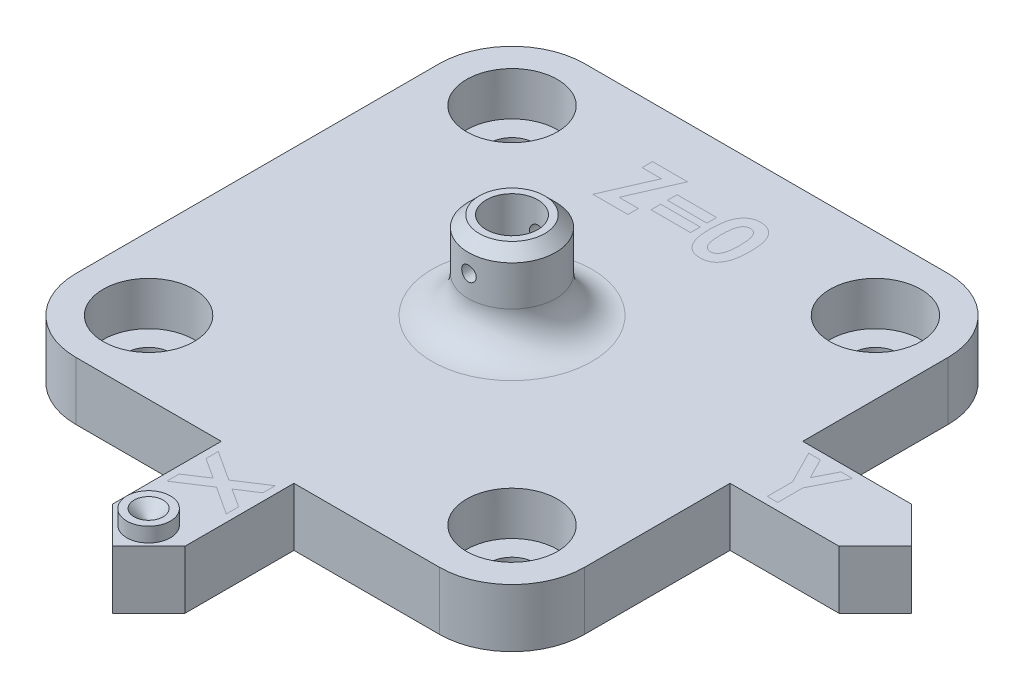
SolidWorks part; units mm, degrees
ref_plane "Front Plane" through (0, 0, 0) normal (0, 0, 1) x (1, 0, 0)
ref_plane "Top Plane" through (0, 0, 0) normal (0, 1, 0) x (1, 0, 0)
ref_plane "Right Plane" through (0, 0, 0) normal (1, 0, 0) x (0, 0, -1)
sketch "Sketch1" plane through (0, 0, 0) normal (0, 1, 0) x (1, 0, 0)
  line L1 (-31, 6) -> (31, 6) construction
  line L2 (-31, 6) -> (-31, -6) construction
  line L3 (-31, -6) -> (31, -6) construction
  line L4 (31, 6) -> (31, -6) construction
  line L5 (-31, 6) -> (31, -6) construction
  line L6 (-31, -6) -> (31, 6) construction
  line L7 (-35, -35) -> (35, -35)
  line L8 (-35, -35) -> (-35, 35)
  line L9 (-35, 35) -> (35, 35)
  line L10 (35, -35) -> (35, 35)
  line L11 (-35, -35) -> (35, 35) construction
  line L12 (-35, 35) -> (35, -35) construction
  circle A0 centre (-25, 0) radius 3.1 construction
  circle A1 centre (25, 0) radius 3.1 construction
  circle A2 centre (0, 0) radius 45 construction
  circle A3 centre (-25, 25) radius 3.1 construction
  circle A4 centre (-25, -75) radius 3.1 construction
  point P0 (0, 0)
  point P14 (0, 0)
  dimension "D2" = 6.2
  dimension "D7" = 90
  dimension "D1" = 12
  dimension "D3" = 6
  dimension "D4" = 25
  dimension "D5" = 25
  dimension "D6" = 25
  dimension "D8" = 100
  dimension "D9" = 10
  dimension "D10" = 10
extrude "Boss-Extrude1" add sketch "Sketch1" along normal blind 8
sketch "Sketch2" plane through (0, 8, 0) normal (0, 1, 0) x (1, 0, 0)
  circle A0 centre (25, 0) radius 3.1 construction
  circle A1 centre (-25, 0) radius 3.1 construction
  circle A2 centre (25, 0) radius 3.1 construction
  circle A3 centre (-25, 0) radius 3.1 construction
  circle A4 centre (-25, 25) radius 3.1 construction
  circle A5 centre (-25, 25) radius 3.1
extrude "Cut-Extrude1" cut sketch "Sketch2" against normal through all
sketch "Sketch8" plane through (0, 8, 0) normal (0, 1, 0) x (1, 0, 0)
  circle A0 centre (-25, 25) radius 6.25
  dimension "D1" = 12.5
extrude "Cut-Extrude6" cut sketch "Sketch8" against normal offset from surface (6 mm away) 2 up to face at (-25, 0, -21.9)
pattern_linear "LPattern1" count 2 spacing 50 along (1, 0, 0) count 2 spacing 50 along (0, 0, 1) of "Cut-Extrude6", "Cut-Extrude1"
sketch "Sketch3" plane through (0, 8, 0) normal (0, 1, 0) x (1, 0, 0)
  line L1 (-6, 6) -> (6, 6) construction
  line L2 (-6, 6) -> (-6, -6) construction
  line L3 (-6, -6) -> (6, -6) construction
  line L4 (6, 6) -> (6, -6) construction
  line L5 (-6, 6) -> (6, -6) construction
  line L6 (-6, -6) -> (6, 6) construction
  line L7 (-31, 6) -> (31, -6) construction
  circle A0 centre (0, 0) radius 6
  point P0 (0, 0)
  dimension "D1" = 12
extrude "Boss-Extrude2" add sketch "Sketch3" along normal blind 12
sketch "Sketch4" plane through (0, 20, 0) normal (0, 1, 0) x (1, 0, 0)
  circle A0 centre (0, 0) radius 3.55
  dimension "D1" = 7.1
extrude "Cut-Extrude2" cut sketch "Sketch4" against normal offset from surface (11 mm away) 1 up to face at (0, 8, -6)
sketch "Sketch5" plane through (0, 9, 0) normal (0, 1, 0) x (1, 0, 0)
  circle A0 centre (0, 0) radius 3.05
  circle A1 centre (0, 0) radius 3.55 construction
  dimension "D1" = 0.5
extrude "Cut-Extrude3" cut sketch "Sketch5" against normal through all
fillet "Fillet1" radius 5 1 edges at (0, 8, -6)
sketch "Sketch7" plane through (0, 0, 0) normal (0, 0, -1) x (-1, 0, 0)
  line L1 (6, 20) -> (-6, 20) construction
  circle A0 centre (0, 16) radius 1
  dimension "D1" = 2
  dimension "D2" = 4
extrude "Cut-Extrude5" cut sketch "Sketch7" against normal through all both and the other way through all
chamfer "Chamfer2" distance 1.5 angle 45 1 edges at (0, 20, 6)
sketch "Sketch9" plane through (0, 0, 0) normal (0, 1, 0) x (1, 0, 0)
  line L0 (-35, -35) -> (35, -35) construction
  line L1 (-5, -55) -> (5, -55)
  line L2 (-5, -55) -> (-5, -35)
  line L3 (-5, -35) -> (5, -35)
  line L4 (5, -55) -> (5, -35)
  line L5 (-5, -55) -> (5, -35) construction
  line L6 (-5, -35) -> (5, -55) construction
  line L7 (35, -35) -> (35, 35) construction
  line L8 (55, -5) -> (35, -5)
  line L9 (55, -5) -> (55, 5)
  line L10 (55, 5) -> (35, 5)
  line L11 (35, -5) -> (35, 5)
  line L12 (55, -5) -> (35, 5) construction
  line L13 (55, 5) -> (35, -5) construction
  point P0 (0, -45)
  point P7 (45, 0)
  dimension "D1" = 10
  dimension "D2" = 20
extrude "Boss-Extrude3" add sketch "Sketch9" along normal up to surface (8 mm away) up to face at (0, 8, -11)
chamfer "Chamfer3" distance 5 angle 45 4 edges at (55, 4, -5) (55, 4, 5) (5, 4, 55) (-5, 4, 55)
sketch "Sketch10" plane through (0, 8, 0) normal (0, 1, 0) x (1, 0, 0)
  line L0 (30, -4) -> (50, -4) construction
  line L1 (-4, -50) -> (-4, -30) construction
  line L2 (50, -5) -> (35, -5) construction
  line L3 (-5, -50) -> (-5, -35) construction
  line L4 (-35, -35) -> (-5, -35) construction
  line L5 (35, -35) -> (35, -5) construction
  line L6 (-15, 20) -> (15, 20) construction
  text T0 "X" font "Century Gothic" height 8
  text T1 "Y" font "Century Gothic" height 8
  text T2 "Z=0" font "Century Gothic" height 8
  point P7 (0, 20)
  dimension "D1" = 20
  dimension "D4" = 5
  dimension "D5" = 5
  dimension "D6" = 20
  dimension "D7" = 30
extrude "Cut-Extrude7" cut sketch "Sketch10" against normal blind 1
sketch "Sketch16" plane through (0, 7, 0) normal (0, 1, 0) x (1, 0, 0)
  line L0 (0.133, -40.7917) -> (4, -43.3093) construction
  line L1 (4, -43.3093) -> (4, -41.617) construction
  line L2 (4, -41.617) -> (1.4311, -39.9455) construction
  line L3 (1.4311, -39.9455) -> (4, -38.2708) construction
  line L4 (4, -38.2708) -> (4, -36.5737) construction
  line L5 (4, -36.5737) -> (0.1298, -39.0978) construction
  line L6 (0.1298, -39.0978) -> (-4, -36.4103) construction
  line L7 (-4, -36.4103) -> (-4, -38.1026) construction
  line L8 (-8.6667, 28) -> (-8.6667, 26.5641)
  line L9 (-8.6667, 26.5641) -> (-6.0096, 26.5641)
  line L10 (-6.0096, 26.5641) -> (-8.8718, 20)
  line L11 (-8.8718, 20) -> (-4.0513, 20)
  line L12 (-4.0513, 20) -> (-4.0513, 21.4359)
  line L13 (-4.0513, 21.4359) -> (-6.7099, 21.4359)
  line L14 (-6.7099, 21.4359) -> (-3.8462, 28)
  line L15 (-3.8462, 28) -> (-8.6667, 28)
  line L16 (-8.6667, 28) -> (-8.6667, 26.5641)
  line L17 (-8.6667, 26.5641) -> (-6.0096, 26.5641)
  line L18 (-6.0096, 26.5641) -> (-8.8718, 20)
  line L19 (-8.8718, 20) -> (-4.0513, 20)
  line L20 (-4.0513, 20) -> (-4.0513, 21.4359)
  line L21 (-4.0513, 21.4359) -> (-6.7099, 21.4359)
  line L22 (-6.7099, 21.4359) -> (-3.8462, 28)
  line L23 (-3.8462, 28) -> (-8.6667, 28)
  line L24 (-4, -38.1026) -> (-1.1683, -39.9455) construction
  line L25 (-1.1683, -39.9455) -> (-4, -41.7917) construction
  line L26 (-4, -41.7917) -> (-4, -43.4872) construction
  line L27 (-4, -43.4872) -> (0.133, -40.7917) construction
  line L28 (36.8205, 4) -> (39.1282, -0.5353) construction
  line L29 (39.1282, -0.5353) -> (39.1282, -4) construction
  line L30 (39.1282, -4) -> (40.5641, -4) construction
  line L31 (40.5641, -4) -> (40.5641, -0.5353) construction
  line L32 (40.5641, -0.5353) -> (42.8718, 4) construction
  line L33 (42.8718, 4) -> (41.2772, 4) construction
  line L34 (41.2772, 4) -> (39.8462, 1.1923) construction
  line L35 (39.8462, 1.1923) -> (38.4183, 4) construction
  line L36 (38.4183, 4) -> (36.8205, 4) construction
  line L37 (-3.0256, 23.4872) -> (-3.0256, 22.1538) construction
  line L38 (-3.0256, 22.1538) -> (2.4103, 22.1538) construction
  line L39 (2.4103, 22.1538) -> (2.4103, 23.4872) construction
  line L40 (2.4103, 23.4872) -> (-3.0256, 23.4872) construction
  line L41 (-3.0256, 25.7436) -> (-3.0256, 24.4103) construction
  line L42 (-3.0256, 24.4103) -> (2.4103, 24.4103) construction
  line L43 (2.4103, 24.4103) -> (2.4103, 25.7436) construction
  line L44 (2.4103, 25.7436) -> (-3.0256, 25.7436) construction
  line L45 (0.133, -40.7917) -> (4, -43.3093)
  line L46 (4, -43.3093) -> (4, -41.617)
  line L47 (4, -41.617) -> (1.4311, -39.9455)
  line L48 (1.4311, -39.9455) -> (4, -38.2708)
  line L49 (4, -38.2708) -> (4, -36.5737)
  line L50 (4, -36.5737) -> (0.1298, -39.0978)
  line L51 (0.1298, -39.0978) -> (-4, -36.4103)
  line L52 (-4, -36.4103) -> (-4, -38.1026)
  line L53 (-4, -38.1026) -> (-1.1683, -39.9455)
  line L54 (-1.1683, -39.9455) -> (-4, -41.7917)
  line L55 (-4, -41.7917) -> (-4, -43.4872)
  line L56 (-4, -43.4872) -> (0.133, -40.7917)
  line L57 (36.8205, 4) -> (39.1282, -0.5353)
  line L58 (39.1282, -0.5353) -> (39.1282, -4)
  line L59 (39.1282, -4) -> (40.5641, -4)
  line L60 (40.5641, -4) -> (40.5641, -0.5353)
  line L61 (40.5641, -0.5353) -> (42.8718, 4)
  line L62 (42.8718, 4) -> (41.2772, 4)
  line L63 (41.2772, 4) -> (39.8462, 1.1923)
  line L64 (39.8462, 1.1923) -> (38.4183, 4)
  line L65 (38.4183, 4) -> (36.8205, 4)
  line L66 (-3.0256, 23.4872) -> (-3.0256, 22.1538)
  line L67 (-3.0256, 22.1538) -> (2.4103, 22.1538)
  line L68 (2.4103, 22.1538) -> (2.4103, 23.4872)
  line L69 (2.4103, 23.4872) -> (-3.0256, 23.4872)
  line L70 (-3.0256, 25.7436) -> (-3.0256, 24.4103)
  line L71 (-3.0256, 24.4103) -> (2.4103, 24.4103)
  line L72 (2.4103, 24.4103) -> (2.4103, 25.7436)
  line L73 (2.4103, 25.7436) -> (-3.0256, 25.7436)
  spline S0 degree 3 poles (-131.7963, 2023.3736) (22.2514, -1.7136) (12.5985, 29.3312) (5.4123, 28.1449) (5.1283, 28.0594) (4.8631, 27.9383) (4.6145, 27.7848) (4.3863, 27.5948) (-0.5437, 22.4383) (20.4757, -3.4865) (-1566.3999, 1265.3933) knots -8.647948 -8.647948 -8.647948 -8.647948 0.131719 0.257624 0.379077 0.499465 0.619088 0.7413 0.867686 9.462064 9.462064 9.462064 9.462064 only from (6.0272, 28.2051) to (3.9904, 27.117) construction
  spline S1 degree 3 poles (-1757.1302, 974.8805) (38.1042, 24.2048) (6.4362, 33.0366) (3.6959, 26.5373) (3.5815, 26.1941) (3.4922, 25.8118) (3.42, 25.3929) (3.3708, 24.9358) (2.4817, 11.8092) (31.1626, -2.1567) (-1996.277, 53.0675) knots -6.083186 -6.083186 -6.083186 -6.083186 0.093438 0.194013 0.303383 0.421624 0.550096 0.689211 0.838929 12.491567 12.491567 12.491567 12.491567 only from (3.9904, 27.117) to (3.3333, 23.9215) construction
  spline S2 degree 3 poles (-1996.5438, 19.6483) (24.8472, 47.8074) (2.8103, 35.3289) (3.3516, 23.185) (3.3788, 22.8467) (3.4153, 22.5307) (3.4611, 22.2369) (3.5179, 21.9659) (3.5874, 21.7179) (3.6654, 21.4906) (3.7552, 21.2822) (3.8507, 21.0881) (3.9548, 20.908) (4.0676, 20.7422) (4.1879, 20.5888) (4.3175, 20.4499) (4.4546, 20.3239) (4.5988, 20.2112) (4.7524, 20.1128) (4.9149, 20.0275) (5.0867, 19.9559) (5.2664, 19.8958) (5.455, 19.8521) (5.6512, 19.8174) (12.3124, 19.2077) (19.7932, 41.6831) (-51.1933, -1979.22) knots -6.292704 -6.292704 -6.292704 -6.292704 0.068139 0.132344 0.192691 0.249232 0.302052 0.351311 0.396892 0.439446 0.479424 0.517927 0.554843 0.590345 0.62485 0.658737 0.691624 0.724128 0.756313 0.788829 0.82192 0.855546 0.889842 0.925133 0.961783 4.454699 4.454699 4.454699 4.454699 only from (3.3333, 23.9215) to (6.0689, 19.7949) construction
  spline S3 degree 3 poles (65.7357, -1979.2509) (-7.5781, 41.8788) (-0.1196, 19.2043) (6.4856, 19.8175) (6.6807, 19.852) (6.8678, 19.8954) (7.044, 19.956) (7.2122, 20.0256) (7.3694, 20.1114) (7.5184, 20.2095) (7.6576, 20.3231) (7.7922, 20.4479) (7.9165, 20.5904) (8.0358, 20.7451) (8.1445, 20.9174) (8.2483, 21.1022) (8.3451, 21.3022) (8.433, 21.518) (8.5147, 21.7521) (8.5824, 22.0084) (8.6393, 22.2862) (8.6879, 22.5855) (8.7234, 22.9071) (8.751, 23.2507) (9.2905, 35.5845) (-12.6765, 48.2224) (2008.6272, 22.718) knots -3.400415 -3.400415 -3.400415 -3.400415 0.037939 0.07404 0.109073 0.142844 0.175687 0.207645 0.239175 0.270414 0.302015 0.334248 0.367526 0.402053 0.437693 0.475324 0.514308 0.555299 0.598705 0.645592 0.695599 0.748917 0.806171 0.866923 0.931509 7.344595 7.344595 7.344595 7.344595 only from (6.0689, 19.7949) to (8.7692, 23.9968) construction
  spline S4 degree 3 poles (2008.5884, 35.2807) (-13.1687, 0.4734) (9.3051, 12.8122) (8.7503, 24.7353) (8.7257, 25.0765) (8.6893, 25.3957) (8.641, 25.693) (8.5839, 25.9685) (8.5173, 26.2231) (8.4382, 26.4567) (8.3497, 26.6721) (8.2533, 26.8725) (8.1477, 27.0582) (8.0338, 27.2302) (7.912, 27.3885) (7.7795, 27.5316) (7.6393, 27.6618) (7.4888, 27.7759) (7.3316, 27.8767) (7.1677, 27.966) (6.9951, 28.0393) (6.8158, 28.1006) (6.6286, 28.1469) (6.4347, 28.1801) (0.3921, 28.8398) (-6.9063, 4.7286) (94.9906, 2026.067) knots -6.101207 -6.101207 -6.101207 -6.101207 0.067325 0.131046 0.191211 0.247637 0.300428 0.349925 0.395975 0.439087 0.479887 0.518688 0.556281 0.592452 0.627384 0.661471 0.69516 0.728117 0.760933 0.793574 0.826381 0.859694 0.893374 0.927966 0.963365 4.094396 4.094396 4.094396 4.094396 only from (8.7692, 23.9968) to (6.0272, 28.2051) construction
  spline S5 degree 3 poles (6.0272, 28.2051) (5.9213, 28.2016) (5.7141, 28.1947) (5.4123, 28.1449) (5.1283, 28.0594) (4.8631, 27.9383) (4.6145, 27.7848) (4.3863, 27.5948) (4.174, 27.3727) (4.0525, 27.2035) (3.9904, 27.117) knots 0 0 0 0 0.131719 0.257624 0.379077 0.499465 0.619088 0.7413 0.867686 1 1 1 1
  spline S6 degree 3 poles (3.9904, 27.117) (3.937, 27.0289) (3.826, 26.846) (3.6959, 26.5373) (3.5815, 26.1941) (3.4922, 25.8118) (3.42, 25.3929) (3.3708, 24.9358) (3.3373, 24.4412) (3.3347, 24.0989) (3.3333, 23.9215) knots 0 0 0 0 0.093438 0.194013 0.303383 0.421624 0.550096 0.689211 0.838929 1 1 1 1
  spline S7 degree 3 poles (3.3333, 23.9215) (3.3341, 23.7938) (3.3356, 23.5458) (3.3516, 23.185) (3.3788, 22.8467) (3.4153, 22.5307) (3.4611, 22.2369) (3.5179, 21.9659) (3.5874, 21.7179) (3.6654, 21.4906) (3.7552, 21.2822) (3.8507, 21.0881) (3.9548, 20.908) (4.0676, 20.7422) (4.1879, 20.5888) (4.3175, 20.4499) (4.4546, 20.3239) (4.5988, 20.2112) (4.7524, 20.1128) (4.9149, 20.0275) (5.0867, 19.9559) (5.2664, 19.8958) (5.455, 19.8521) (5.6512, 19.8174) (5.857, 19.7985) (5.9973, 19.7961) (6.0689, 19.7949) knots 0 0 0 0 0.068139 0.132344 0.192691 0.249232 0.302052 0.351311 0.396892 0.439446 0.479424 0.517927 0.554843 0.590345 0.62485 0.658737 0.691624 0.724128 0.756313 0.788829 0.82192 0.855546 0.889842 0.925133 0.961783 1 1 1 1
  spline S8 degree 3 poles (6.0689, 19.7949) (6.1405, 19.7961) (6.2803, 19.7984) (6.4856, 19.8175) (6.6807, 19.852) (6.8678, 19.8954) (7.044, 19.956) (7.2122, 20.0256) (7.3694, 20.1114) (7.5184, 20.2095) (7.6576, 20.3231) (7.7922, 20.4479) (7.9165, 20.5904) (8.0358, 20.7451) (8.1445, 20.9174) (8.2483, 21.1022) (8.3451, 21.3022) (8.433, 21.518) (8.5147, 21.7521) (8.5824, 22.0084) (8.6393, 22.2862) (8.6879, 22.5855) (8.7234, 22.9071) (8.751, 23.2507) (8.767, 23.6163) (8.7685, 23.8675) (8.7692, 23.9968) knots 0 0 0 0 0.037939 0.07404 0.109073 0.142844 0.175687 0.207645 0.239175 0.270414 0.302015 0.334248 0.367526 0.402053 0.437693 0.475324 0.514308 0.555299 0.598705 0.645592 0.695599 0.748917 0.806171 0.866923 0.931509 1 1 1 1
  spline S9 degree 3 poles (8.7692, 23.9968) (8.7685, 24.1245) (8.7671, 24.373) (8.7503, 24.7353) (8.7257, 25.0765) (8.6893, 25.3957) (8.641, 25.693) (8.5839, 25.9685) (8.5173, 26.2231) (8.4382, 26.4567) (8.3497, 26.6721) (8.2533, 26.8725) (8.1477, 27.0582) (8.0338, 27.2302) (7.912, 27.3885) (7.7795, 27.5316) (7.6393, 27.6618) (7.4888, 27.7759) (7.3316, 27.8767) (7.1677, 27.966) (6.9951, 28.0393) (6.8158, 28.1006) (6.6286, 28.1469) (6.4347, 28.1801) (6.2334, 28.2021) (6.0967, 28.2041) (6.0272, 28.2051) knots 0 0 0 0 0.067325 0.131046 0.191211 0.247637 0.300428 0.349925 0.395975 0.439087 0.479887 0.518688 0.556281 0.592452 0.627384 0.661471 0.69516 0.728117 0.760933 0.793574 0.826381 0.859694 0.893374 0.927966 0.963365 1 1 1 1
  spline S15 degree 3 poles (3006.8723, 64.4156) (-23.2912, -1.2869) (7.9892, 12.0725) (7.3132, 24.714) (7.2872, 25.0323) (7.2493, 25.3196) (7.2004, 25.5768) (7.1402, 25.8037) (7.0693, 26.0008) (6.9851, 26.1679) (6.8919, 26.31) (6.793, 26.4318) (6.6879, 26.5359) (6.5768, 26.6225) (6.4572, 26.6887) (6.3313, 26.7354) (2.0838, 27.6423) (-5.7225, -5.7114) (307.3534, 3011.3674) knots -10.943971 -10.943971 -10.943971 -10.943971 0.112115 0.215802 0.310203 0.395993 0.47341 0.542778 0.604548 0.659357 0.708764 0.755356 0.798687 0.840017 0.880203 0.919733 0.959049 4.723306 4.723306 4.723306 4.723306 only from (7.3333, 23.9968) to (6.0625, 26.7692)
  spline S16 degree 3 poles (-396.7877, 2999.2649) (20.9753, -12.5004) (10.4324, 28.0237) (5.6977, 26.7109) (5.5292, 26.6343) (5.401, 26.5422) (5.305, 26.4539) (5.238, 26.374) (5.1733, 26.2848) (5.1162, 26.1823) (5.0623, 26.0702) (5.0096, 25.9481) (4.9664, 25.8128) (4.9239, 25.6666) (4.8867, 25.5057) (4.8556, 25.3285) (4.8278, 25.1341) (4.8083, 24.9222) (4.7902, 24.693) (4.7773, 24.4462) (4.4295, 7.4879) (21.3435, -9.4959) (-2994.7669, -7.4366) knots -4.028583 -4.028583 -4.028583 -4.028583 0.053834 0.105543 0.158054 0.211987 0.240207 0.269794 0.301343 0.334608 0.370284 0.408089 0.448681 0.492069 0.538664 0.590371 0.646388 0.707195 0.772947 0.843643 0.919308 15.328481 15.328481 15.328481 15.328481 only from (6.0625, 26.7692) to (4.7692, 23.9054)
  spline S17 degree 3 poles (-2994.933, 19.8201) (30.7114, 51.9921) (4.1649, 37.4469) (4.7882, 23.2142) (4.8177, 22.9085) (4.8544, 22.631) (4.9059, 22.3833) (4.9651, 22.1633) (5.0383, 21.9737) (5.1229, 21.8117) (5.2166, 21.6739) (5.3182, 21.5568) (5.4245, 21.4553) (5.5386, 21.3729) (5.6603, 21.3098) (5.7886, 21.2644) (10.1593, 20.3639) (17.9321, 53.1736) (-286.2462, -2964.186) knots -12.639915 -12.639915 -12.639915 -12.639915 0.110734 0.212341 0.305502 0.389835 0.46669 0.535262 0.596763 0.651066 0.701036 0.74786 0.791833 0.834284 0.875334 0.916035 0.957652 4.913375 4.913375 4.913375 4.913375 only from (4.7692, 23.9054) to (6.0625, 21.2308)
  spline S18 degree 3 poles (288.3674, -2965.3126) (-5.2957, 53.9676) (2.1906, 20.4012) (6.3241, 21.2614) (6.4456, 21.3049) (6.5598, 21.3664) (6.667, 21.4446) (6.7667, 21.5399) (10.0814, 25.6403) (-12.3943, 47.4246) (2487.2197, -1665.6184) knots -11.232017 -11.232017 -11.232017 -11.232017 0.124035 0.242846 0.360342 0.479042 0.599334 0.725488 0.858549 15.106951 15.106951 15.106951 15.106951 only from (6.0625, 21.2308) to (6.9391, 21.7804)
  spline S19 degree 3 poles (2708.4682, -1282.2352) (-29.8064, 26.3531) (4.9751, 16.4582) (7.1178, 22.1731) (7.1839, 22.4093) (7.2408, 22.6729) (7.2797, 22.9652) (7.3132, 23.2841) (7.9635, 37.2578) (-19.872, 51.529) (3007.087, 22.3277) knots -7.73203 -7.73203 -7.73203 -7.73203 0.088871 0.186355 0.294078 0.412237 0.541778 0.682703 0.835096 18.984053 18.984053 18.984053 18.984053 only from (6.9391, 21.7804) to (7.3333, 23.9968)
  spline S20 degree 3 poles (7.3333, 23.9968) (7.3328, 24.1229) (7.3318, 24.3656) (7.3132, 24.714) (7.2872, 25.0323) (7.2493, 25.3196) (7.2004, 25.5768) (7.1402, 25.8037) (7.0693, 26.0008) (6.9851, 26.1679) (6.8919, 26.31) (6.793, 26.4318) (6.6879, 26.5359) (6.5768, 26.6225) (6.4572, 26.6887) (6.3313, 26.7354) (6.1989, 26.7637) (6.1086, 26.7673) (6.0625, 26.7692) knots 0 0 0 0 0.112115 0.215802 0.310203 0.395993 0.47341 0.542778 0.604548 0.659357 0.708764 0.755356 0.798687 0.840017 0.880203 0.919733 0.959049 1 1 1 1
  spline S21 degree 3 poles (6.0625, 26.7692) (5.9997, 26.7663) (5.8765, 26.7604) (5.6977, 26.7109) (5.5292, 26.6343) (5.401, 26.5422) (5.305, 26.4539) (5.238, 26.374) (5.1733, 26.2848) (5.1162, 26.1823) (5.0623, 26.0702) (5.0096, 25.9481) (4.9664, 25.8128) (4.9239, 25.6666) (4.8867, 25.5057) (4.8556, 25.3285) (4.8278, 25.1341) (4.8083, 24.9222) (4.7902, 24.693) (4.7773, 24.4462) (4.7718, 24.1816) (4.7701, 23.9995) (4.7692, 23.9054) knots 0 0 0 0 0.053834 0.105543 0.158054 0.211987 0.240207 0.269794 0.301343 0.334608 0.370284 0.408089 0.448681 0.492069 0.538664 0.590371 0.646388 0.707195 0.772947 0.843643 0.919308 1 1 1 1
  spline S22 degree 3 poles (4.7692, 23.9054) (4.7707, 23.7836) (4.7735, 23.5501) (4.7882, 23.2142) (4.8177, 22.9085) (4.8544, 22.631) (4.9059, 22.3833) (4.9651, 22.1633) (5.0383, 21.9737) (5.1229, 21.8117) (5.2166, 21.6739) (5.3182, 21.5568) (5.4245, 21.4553) (5.5386, 21.3729) (5.6603, 21.3098) (5.7886, 21.2644) (5.9235, 21.2366) (6.0159, 21.2327) (6.0625, 21.2308) knots 0 0 0 0 0.110734 0.212341 0.305502 0.389835 0.46669 0.535262 0.596763 0.651066 0.701036 0.74786 0.791833 0.834284 0.875334 0.916035 0.957652 1 1 1 1
  spline S23 degree 3 poles (6.0625, 21.2308) (6.1075, 21.2321) (6.1956, 21.2347) (6.3241, 21.2614) (6.4456, 21.3049) (6.5598, 21.3664) (6.667, 21.4446) (6.7667, 21.5399) (6.8583, 21.6531) (6.9116, 21.7371) (6.9391, 21.7804) knots 0 0 0 0 0.124035 0.242846 0.360342 0.479042 0.599334 0.725488 0.858549 1 1 1 1
  spline S24 degree 3 poles (6.9391, 21.7804) (6.9715, 21.8396) (7.0393, 21.9637) (7.1178, 22.1731) (7.1839, 22.4093) (7.2408, 22.6729) (7.2797, 22.9652) (7.3132, 23.2841) (7.3293, 23.6312) (7.332, 23.8718) (7.3333, 23.9968) knots 0 0 0 0 0.088871 0.186355 0.294078 0.412237 0.541778 0.682703 0.835096 1 1 1 1
  dimension "D1" = 0
  dimension "D2" = 0
extrude "Boss-Extrude5" add sketch "Sketch16" along normal up to surface (1 mm away) separate body up to face at (0.0438, 8, 39.9452)
sketch "Sketch12" plane through (0, 8, 0) normal (0, 1, 0) x (1, 0, 0)
  circle A0 centre (0, -50) radius 3
  dimension "D1" = 6
  dimension "D2" = 50
extrude "Boss-Extrude4" add sketch "Sketch12" along normal blind 2
sketch "Sketch13" plane through (0, 10, 0) normal (0, 1, 0) x (1, 0, 0)
  circle A0 centre (0, -50) radius 2
  dimension "D1" = 4
extrude "Cut-Extrude8" cut sketch "Sketch13" against normal blind 2
chamfer "Chamfer4" distance 2 angle 45 1 edges at (0, 8, 52)
fillet "Fillet2" radius 10 4 edges at (35, 4, -35) (-35, 4, -35) (35, 4, 35) (-35, 4, 35)
equation "\"D5@Sketch1\"=\"D4@Sketch1\""
equation "\"D10@Sketch1\"=\"D9@Sketch1\""
equation "\"D5@Sketch10\"=\"D4@Sketch10\""
